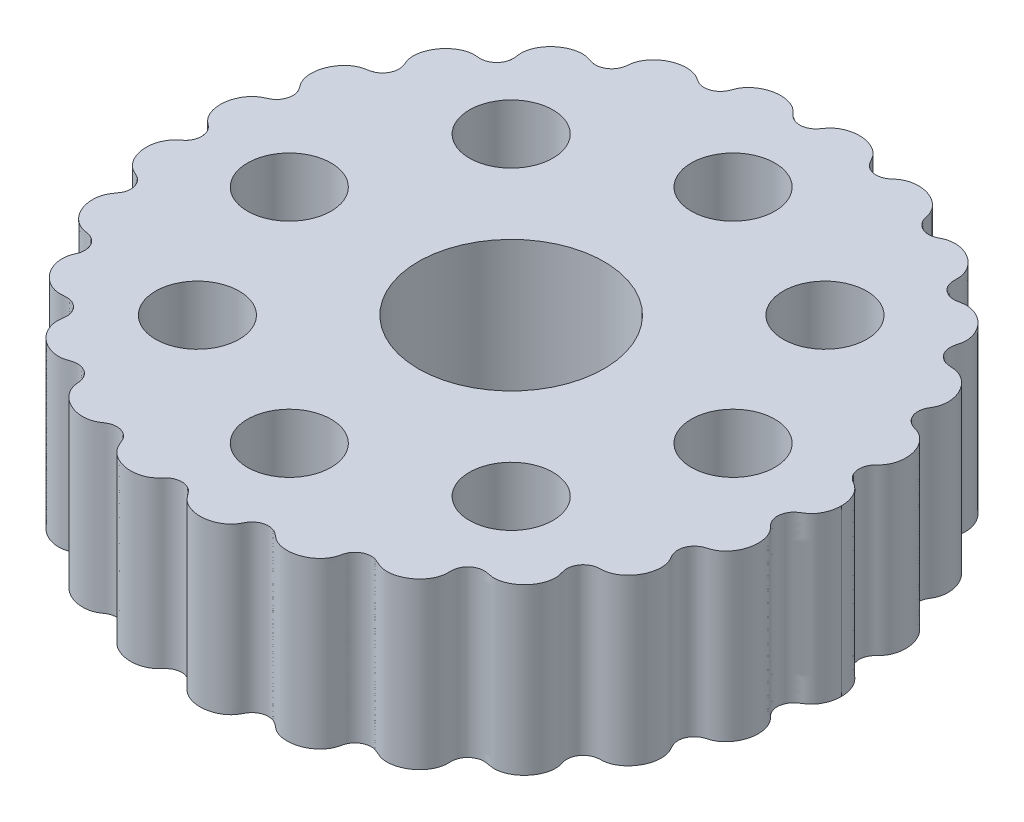
SolidWorks part; units mm, degrees
ref_plane "Front Plane" through (0, 0, 0) normal (0, 0, 1) x (1, 0, 0)
ref_plane "Top Plane" through (0, 0, 0) normal (0, 1, 0) x (1, 0, 0)
ref_plane "Right Plane" through (0, 0, 0) normal (1, 0, 0) x (0, 0, -1)
sketch "Sketch2" plane through (0, 0, 0) normal (0, 1, 0) x (1, 0, 0)
  line L0 (-31.5, 0) -> (33.5, 0) construction
  circle A0 centre (0, 0) radius 9
  circle A1 centre (0, 0) radius 21.5 construction
  circle A2 centre (0, 21.5) radius 4.05
  circle A3 centre (15.2028, 15.2028) radius 4.05
  circle A4 centre (21.5, 0) radius 4.05
  circle A5 centre (15.2028, -15.2028) radius 4.05
  circle A6 centre (0, -21.5) radius 4.05
  circle A7 centre (-15.2028, -15.2028) radius 4.05
  circle A8 centre (-21.5, 0) radius 4.05
  circle A9 centre (-15.2028, 15.2028) radius 4.05
  spline S0 degree 4 number of poles 351 (32.3077, -8.7825) -> (-30.5369, -7.93) construction
  spline S1 degree 4 number of poles 295 (33.5, 0) -> (-31.5, 0) construction
  spline S2 degree 4 number of poles 295 (33.5, 0) -> (-31.5, 0) construction
  spline S3 degree 1 poles (32, 0) (-30, 0) knots 0 0 1 1 construction
  spline S4 degree 1 poles (32, 0) (-30, 0) knots 0 0 1 1 construction
  spline S5 degree 3 number of poles 521 (32, 0) -> (-30, 0)
  spline S6 degree 3 number of poles 521 (-30, 0) -> (32, 0)
  point P29 (0, 0)
  dimension "D2" = 18
  dimension "D3" = 43
  dimension "D4" = 8.1
  dimension "D1" = 1.5
  dimension "D5" = 8
extrude "Boss-Extrude1" add sketch "Sketch2" along normal blind 16
